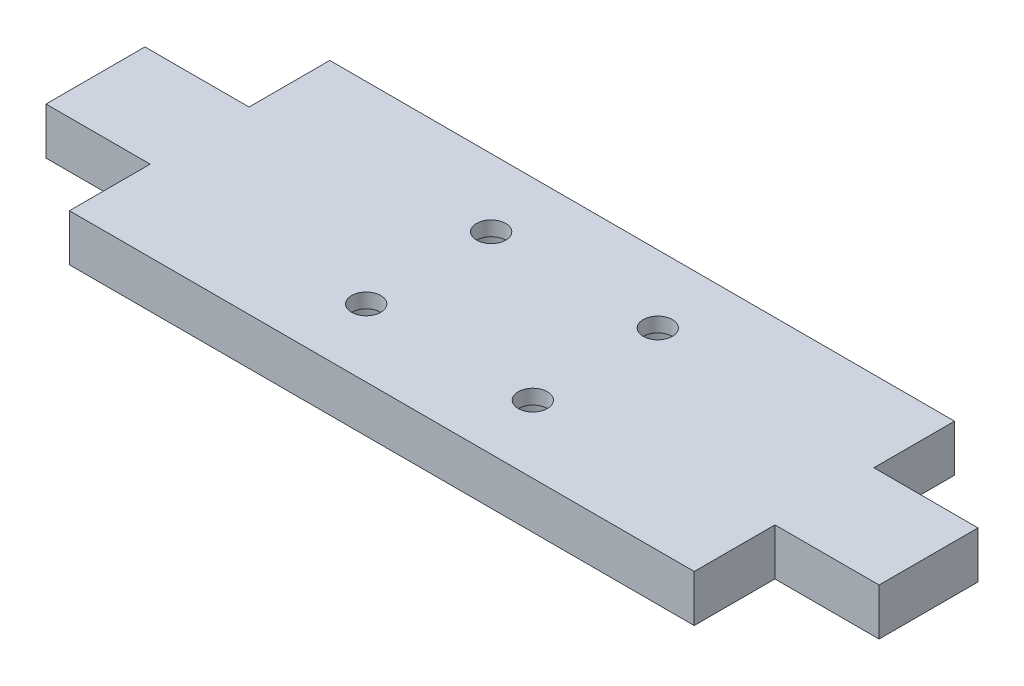
SolidWorks part; units mm, degrees
ref_plane "Front Plane" through (0, 0, 0) normal (0, 0, 1) x (1, 0, 0)
ref_plane "Top Plane" through (0, 0, 0) normal (0, 1, 0) x (1, 0, 0)
ref_plane "Right Plane" through (0, 0, 0) normal (1, 0, 0) x (0, 0, -1)
sketch "Sketch1" plane through (0, 0, 0) normal (1, 0, 0) x (0, 0, -1)
  line L1 (-12.5, -2.25) -> (12.5, -2.25)
  line L2 (-12.5, -2.25) -> (-12.5, 2.25)
  line L3 (-12.5, 2.25) -> (12.5, 2.25)
  line L4 (12.5, -2.25) -> (12.5, 2.25)
  line L5 (-12.5, -2.25) -> (12.5, 2.25) construction
  line L6 (-12.5, 2.25) -> (12.5, -2.25) construction
  point P0 (0, 0)
  dimension "D1" = 4.5
  dimension "D2" = 25
extrude "Boss-Extrude1" add sketch "Sketch1" along normal mid plane 60
sketch "Sketch2" plane through (30, 0, 0) normal (1, 0, 0) x (0, 0, -1)
  line L0 (-12.5, -2.25) -> (12.5, -2.25) construction
  line L1 (-4.75, -2.25) -> (4.75, -2.25)
  line L2 (-4.75, -2.25) -> (-4.75, 2.25)
  line L3 (-4.75, 2.25) -> (4.75, 2.25)
  line L4 (4.75, -2.25) -> (4.75, 2.25)
  point P0 (-4.75, 0)
  point P5 (4.95, 1.7112)
  point P6 (0, -0.8995)
  point P8 (0, 0)
  point P11 (0, 2.25)
  dimension "D1" = 9.5
  dimension "D3" = 4.5
extrude "Boss-Extrude2" add sketch "Sketch2" along normal blind 10
mirror "Mirror1" about plane through (0, 0, 0) normal (1, 0, 0) of "Boss-Extrude2"
sketch "Sketch3" plane through (0, -2.25, 0) normal (0, -1, 0) x (1, 0, 0)
  point P0 (8, 6)
  point P1 (8, -6)
  point P2 (-8, -6)
  point P3 (-8, 6)
  dimension "D1" = 16
  dimension "D2" = 16
  dimension "D3" = 12
  dimension "D4" = 12
  dimension "D5" = 6
  dimension "D6" = 8
hole_wizard "CBORE for M3 SBHCS2" positions "Sketch4" profile "Sketch5" counterbore size "M3" standard "ANSI Metric" end condition through all
sketch "Sketch4" plane through (0, -2.25, 0) normal (0, -1, 0) x (-1, 0, 0)
  point P0 (-8, 6)
  point P3 (8, 6)
  point P6 (8, -6)
  point P9 (-8, -6)
sketch "Sketch5" plane through (8, -2.25, -6) normal (1, 0, 0) x (0, 0, -1)
  line L0 (0, 0) -> (0, 4.5)
  line L1 (0, 4.5) -> (1.4, 4.5)
  line L3 (1.4, 4.5) -> (1.4, 3.1)
  line L4 (1.4, 3.1) -> (2.75, 3.1)
  line L5 (2.75, 3.1) -> (2.75, 0)
  line L7 (2.75, 0) -> (0, 0)
  line L11 (0, -6.35) -> (0, 107.95) construction
  dimension "Thru Hole Dia." = 2.8
  dimension "Thru Hole Depth" = 4.5
  dimension "C'Bore Dia." = 5.5
  dimension "C'Bore Depth" = 3.1
